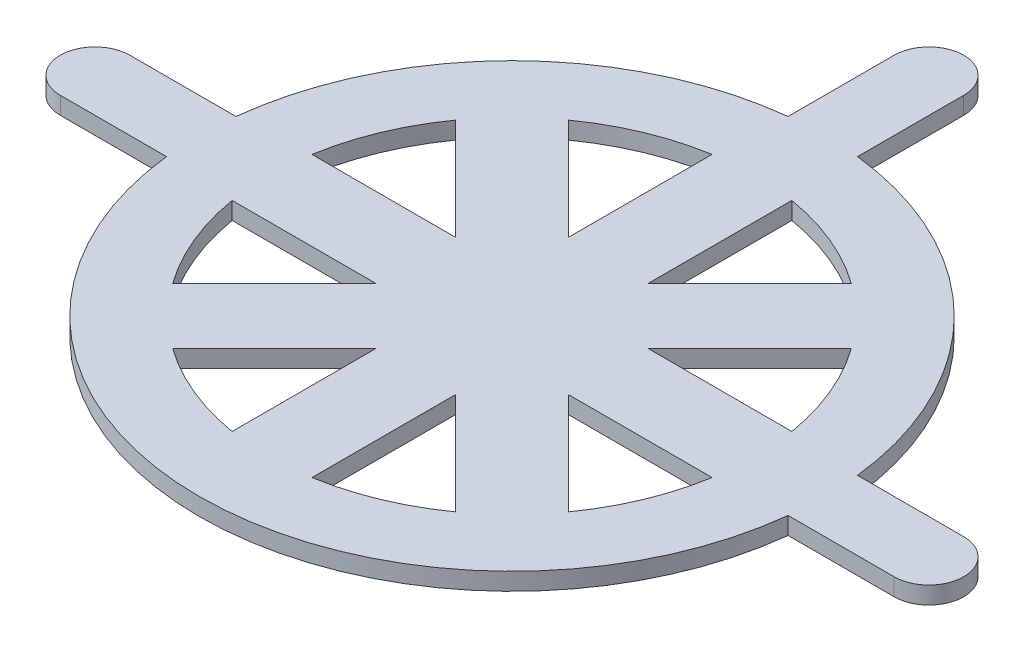
SolidWorks part; units mm, degrees
ref_plane "Front Plane" through (0, 0, 0) normal (0, 0, 1) x (1, 0, 0)
ref_plane "Top Plane" through (0, 0, 0) normal (0, 1, 0) x (1, 0, 0)
ref_plane "Right Plane" through (0, 0, 0) normal (1, 0, 0) x (0, 0, -1)
sketch "Sketch1" plane through (0, 0, 0) normal (0, 1, 0) x (1, 0, 0)
  line L0 (0, 28.575) -> (0, 38.1) construction
  line L1 (-3.175, 38.1) -> (-3.175, 28.3981)
  line L3 (3.175, 38.1) -> (3.175, 28.3981)
  line L4 (-38.1, -3.175) -> (-28.3981, -3.175)
  line L5 (-38.1, 3.175) -> (-28.3981, 3.175)
  line L6 (0, 38.1) -> (0, 0) construction
  line L7 (0, 0) -> (-38.1, 0) construction
  line L8 (38.1, -3.175) -> (28.3981, -3.175)
  line L9 (38.1, 3.175) -> (28.3981, 3.175)
  line L10 (3.6451, 21.9241) -> (3.6451, 8.8)
  line L11 (-3.6451, 21.9241) -> (-3.6451, 8.8)
  line L12 (12.9252, 18.0801) -> (3.6451, 8.8)
  line L13 (18.0801, 12.9252) -> (8.8, 3.6451)
  line L14 (21.9241, 3.6451) -> (8.8, 3.6451)
  line L15 (21.9241, -3.6451) -> (8.8, -3.6451)
  line L16 (18.0801, -12.9252) -> (8.8, -3.6451)
  line L17 (12.9252, -18.0801) -> (3.6451, -8.8)
  line L18 (3.6451, -21.9241) -> (3.6451, -8.8)
  line L19 (-3.6451, -21.9241) -> (-3.6451, -8.8)
  line L20 (-12.9252, -18.0801) -> (-3.6451, -8.8)
  line L21 (-18.0801, -12.9252) -> (-8.8, -3.6451)
  line L22 (-21.9241, -3.6451) -> (-8.8, -3.6451)
  line L23 (-21.9241, 3.6451) -> (-8.8, 3.6451)
  line L24 (-18.0801, 12.9252) -> (-8.8, 3.6451)
  line L25 (-12.9252, 18.0801) -> (-3.6451, 8.8)
  circle A0 centre (0, 0) radius 28.575
  arc A1 (3.175, 38.1) -> (-3.175, 38.1) centre (0, 38.1) ccw
  arc A2 (-38.1, 3.175) -> (-38.1, -3.175) centre (-38.1, 0) ccw
  arc A3 (38.1, 3.175) -> (38.1, -3.175) centre (38.1, 0) cw
  circle A4 centre (0, 0) radius 22.225
  circle A5 centre (0, 0) radius 9.525
  point P55 (0, 0)
  dimension "D1" = 57.15
  dimension "D2" = 6.35
  dimension "D5" = 19.05
  dimension "D6" = 6.35
  dimension "D3" = 9.525
  dimension "D4" = 2
  dimension "D8" = 8
extrude "Boss-Extrude1" add sketch "Sketch1" along normal blind 1.5875 contours L5 A2 L4 A0 | A0 A4 | L3 A1 L1 A0 | A3 L9 A0 L8 | A5 L13 A4 L12 | A5 L10 A4 L11 | A5 L25 A4 L24 | A5 L23 A4 L22 | A5 L21 A4 L20 | A5 | A5 L19 A4 L18 | A5 L17 A4 L16 | A5 L15 A4 L14 region at (0, 0, -34.5755) region at (0, 0, -27.7668) region at (-34.5755, 0, 0) region at (34.5755, 0, 0) region at (0, 0, -15.7046) region at (11.1048, 0, -11.1048) region at (0, 0, 0) region at (15.7046, 0, 0) region at (-11.1048, 0, -11.1048) region at (-15.7046, 0, 0) region at (11.1048, 0, 11.1048) region at (-11.1048, 0, 11.1048) region at (0, 0, 15.7046)
